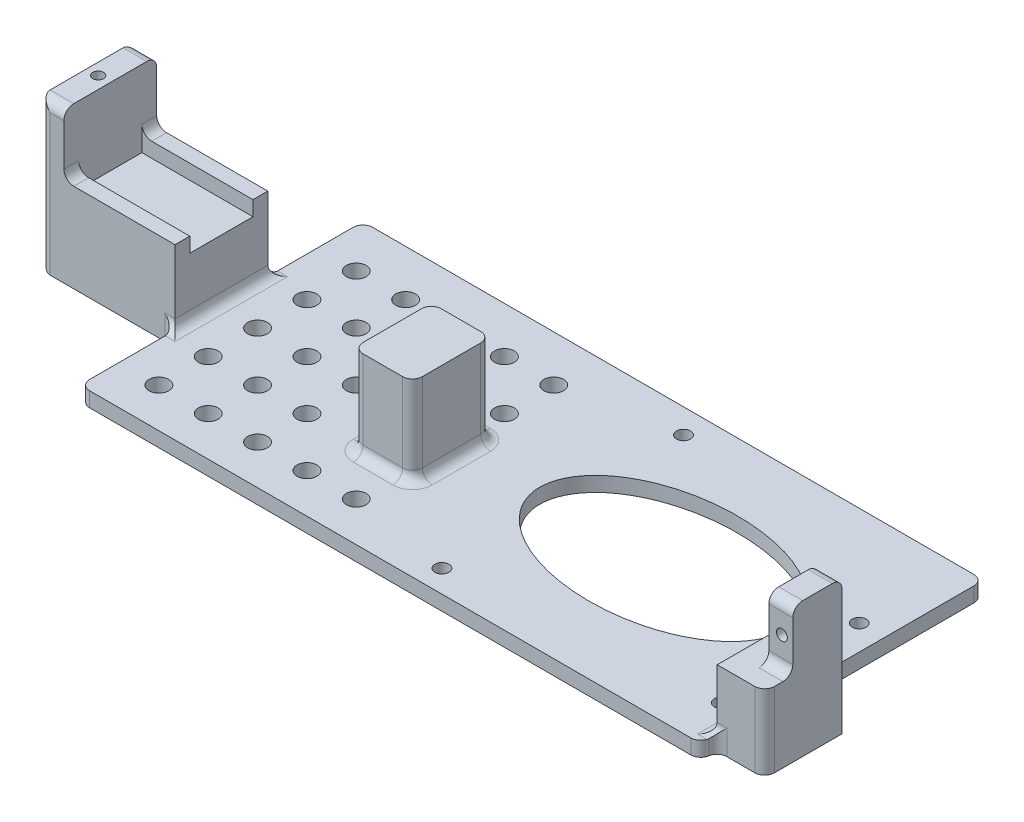
SolidWorks part; units mm, degrees
ref_plane "Front Plane" through (0, 0, 0) normal (0, 0, 1) x (1, 0, 0)
ref_plane "Top Plane" through (0, 0, 0) normal (0, 1, 0) x (1, 0, 0)
ref_plane "Right Plane" through (0, 0, 0) normal (1, 0, 0) x (0, 0, -1)
sketch "Arduino Base" plane through (0, 0, 0) normal (0, 1, 0) x (1, 0, 0)
  line L0 (-36.29, 28.67) -> (36.29, 28.67)
  line L1 (-34.29, -26.67) -> (34.29, -26.67) construction
  line L2 (-34.29, -26.67) -> (-34.29, 26.67) construction
  line L3 (-34.29, 26.67) -> (34.29, 26.67) construction
  line L4 (34.29, -26.67) -> (34.29, 26.67) construction
  line L5 (-34.29, -26.67) -> (34.29, 26.67) construction
  line L6 (-34.29, 26.67) -> (34.29, -26.67) construction
  line L7 (36.29, -28.67) -> (36.29, 28.67)
  line L8 (-36.29, -28.67) -> (36.29, -28.67)
  line L9 (-36.29, -28.67) -> (-36.29, 28.67)
  circle A0 centre (-19.59, 23.71) radius 1.4224
  circle A1 centre (31.21, 8.51) radius 1.4224
  circle A2 centre (31.21, -19.43) radius 1.4224
  circle A3 centre (-20.69, -24.13) radius 1.4224
  point P0 (0, 0)
  dimension "D3" = 2.8448
  dimension "D4" = 2.54
  dimension "D11" = 2
  dimension "D1" = 53.34
  dimension "D2" = 68.58
  dimension "D5" = 27.94
  dimension "D6" = 4.7
  dimension "D7" = 50.8
  dimension "D8" = 15.2
  dimension "D9" = 51.9
  dimension "D10" = 65.5
extrude "Arduino" add sketch "Arduino Base" along normal blind 3
sketch "Sketch5" plane through (0, 0, 0) normal (0, -1, 0) x (1, 0, 0)
  ellipse E0 centre (0, 0) end of major axis (-25, 0) minor radius 15
  dimension "D1" = 15
  dimension "D2" = 25
extrude "Cut-Extrude1" cut sketch "Sketch5" against normal up to surface (3 mm away) up to face at (0, 3, 0)
fillet "Fillet2" radius 2 2 edges at (36.29, 1.5, -28.67) (36.29, 1.5, 28.67)
sketch "Battery Base" plane through (-36.29, 0, 0) normal (-1, 0, 0) x (0, 0, 1)
  line L1 (-28.67, 3) -> (28.67, 3)
  line L2 (-28.67, 3) -> (-28.67, 0)
  line L3 (-28.67, 0) -> (28.67, 0)
  line L4 (28.67, 3) -> (28.67, 0)
extrude "Battery" add sketch "Battery Base" along normal blind 53.2
sketch "Sketch4" plane through (0, 3, 0) normal (0, 1, 0) x (1, 0, 0)
  line L0 (-89.49, -28.67) -> (34.29, -28.67) construction
  line L1 (-89.49, 28.67) -> (-36.29, 28.67) construction
  line L2 (-89.49, 28.67) -> (-89.49, -28.67) construction
  line L3 (-89.49, -28.67) -> (-36.29, -28.67) construction
  line L4 (-36.29, 28.67) -> (-36.29, -28.67) construction
  line L5 (-38.29, -12.49) -> (-50.29, -12.49)
  line L6 (-36.29, 5.33) -> (-52.29, 5.33) construction
  line L7 (-36.29, 5.33) -> (-36.29, -14.49) construction
  line L8 (-36.29, -14.49) -> (-52.29, -14.49) construction
  line L9 (-52.29, 5.33) -> (-52.29, -14.49) construction
  line L10 (-50.29, 3.33) -> (-50.29, -12.49)
  line L11 (-38.29, 3.33) -> (-50.29, 3.33)
  line L12 (-38.29, 3.33) -> (-38.29, -12.49)
  line L13 (-38.29, 28.67) -> (-38.29, -28.67) construction
  line L14 (-36.29, 3.33) -> (-50.29, 3.33) construction
  line L15 (-36.29, -12.49) -> (-50.29, -12.49) construction
  dimension "D1" = 53.2
  dimension "D2" = 14.18
  dimension "D3" = 34
  dimension "D4" = 16
  dimension "D5" = 2
extrude "Boss-Extrude3" add sketch "Sketch4" along normal blind 18
fillet "Fillet1" radius 2 8 edges at (-38.29, 12, -3.33) (-38.29, 12, 12.49) (-50.29, 12, 12.49) (-50.29, 12, -3.33) (-44.29, 3, 12.49) (-38.29, 3, 4.58) (-50.29, 3, 4.58) (-44.29, 3, -3.33)
sketch "Sketch6" plane through (0, 3, 0) normal (0, 1, 0) x (1, 0, 0)
  line L0 (-89.49, -28.67) -> (-89.49, 28.67) construction
  line L1 (-89.49, 6.4) -> (-111.99, 6.4)
  line L2 (-89.49, 6.4) -> (-89.49, -6.4)
  line L3 (-89.49, -6.4) -> (-111.99, -6.4)
  line L4 (-111.99, 6.4) -> (-111.99, -6.4)
  point P6 (-89.49, 0)
  point P7 (-89.49, 0)
  dimension "D1" = 22.5
  dimension "D2" = 12.8
extrude "Boss-Extrude4" add sketch "Sketch6" against normal up to surface (3 mm away) and the other way blind 12 up to face at (-25, 0, 0)
sketch "Sketch7" plane through (0, 0, 6.4) normal (0, 0, 1) x (1, 0, 0)
  line L0 (-111.99, 15) -> (-89.49, 15) construction
  line L1 (-89.49, 0) -> (-114.99, 0)
  line L2 (-89.49, 0) -> (-89.49, 18)
  line L3 (-89.49, 18) -> (-114.99, 18)
  line L4 (-114.99, 0) -> (-114.99, 18)
  line L5 (-111.99, 15) -> (-111.99, 0) construction
  dimension "D1" = 3
  dimension "D2" = 3
extrude "Boss-Extrude5" add sketch "Sketch7" along normal blind 3
mirror "Mirror1" about plane through (0, 0, 0) normal (0, 0, 1) of "Boss-Extrude5"
sketch "Sketch8" plane through (-111.99, 0, 0) normal (-1, 0, 0) x (0, 0, 1)
  line L1 (-6.4, 18) -> (6.4, 18)
  line L2 (-6.4, 18) -> (-6.4, 0)
  line L3 (-6.4, 0) -> (6.4, 0)
  line L4 (6.4, 18) -> (6.4, 0)
extrude "Boss-Extrude6" add sketch "Sketch8" along normal up to surface (3 mm away) up to face at (-114.99, 9, -7.9)
sketch "Sketch10" plane through (-114.99, 0, 0) normal (-1, 0, 0) x (0, 0, 1)
  line L0 (9.4, 18) -> (9.4, 0) construction
  line L1 (-9.4, 0) -> (9.4, 0)
  line L2 (-9.4, 0) -> (-9.4, 30.5)
  line L3 (-9.4, 30.5) -> (9.4, 30.5)
  line L4 (9.4, 0) -> (9.4, 30.5)
  dimension "D1" = 30.5
extrude "Boss-Extrude7" add sketch "Sketch10" along normal blind 1.8 and the other way up to surface (3 mm away) other way up to face at (-111.99, 16.5, 0)
fillet "Fillet4" radius 2 2 edges at (-111.99, 18, 7.9) (-111.99, 18, -7.9)
sketch "Sketch11" plane through (0, 30.5, 0) normal (0, 1, 0) x (1, 0, 0)
  line L0 (-111.99, 9.4) -> (-116.79, 9.4) construction
  line L1 (-111.99, 9.4) -> (-111.99, -9.4) construction
  circle A0 centre (-114.45, 0) radius 1.1
  dimension "D1" = 2.2
  dimension "D2" = 9.4
  dimension "D3" = 2.46
extrude "Cut-Extrude2" cut sketch "Sketch11" against normal up to surface (15.5 mm away) up to face at (-100.74, 15, 0)
fillet "Fillet5" radius 2 2 edges at (-89.49, 1.5, -9.4) (-89.49, 1.5, 9.4)
fillet "Fillet6" radius 2 1 edges at (-89.49, 3, 0)
fillet "Fillet7" radius 2 5 edges at (-116.79, 0, 0) (-116.79, 15.25, -9.4) (-116.79, 15.25, 9.4) (-114.39, 30.5, -9.4) (-114.39, 30.5, 9.4)
sketch "Sketch12" plane through (0, 0, 0) normal (0, -1, 0) x (1, 0, 0)
  line L0 (36.29, 25.33) -> (56.29, 25.33) construction
  line L1 (36.29, 26.67) -> (36.29, -26.67) construction
  line L2 (-89.49, 28.67) -> (34.29, 28.67) construction
  line L4 (36.29, 25.33) -> (45.89, 25.33)
  line L5 (36.29, 25.33) -> (36.29, 9.63)
  line L6 (36.29, 9.63) -> (45.89, 9.63)
  line L7 (45.89, 25.33) -> (45.89, 9.63)
  dimension "D1" = 3.34
  dimension "D2" = 20
  dimension "D3" = 15.7
  dimension "D4" = 9.6
extrude "Boss-Extrude8" add sketch "Sketch12" against normal blind 15.16
fillet "Fillet8" radius 2 1 edges at (36.29, 3, 17.48)
sketch "Sketch13" plane through (0, 15.16, 0) normal (0, 1, 0) x (1, 0, 0)
  line L1 (45.89, -9.63) -> (41.04, -9.63)
  line L2 (45.89, -9.63) -> (45.89, -19.63)
  line L3 (45.89, -19.63) -> (41.04, -19.63)
  line L4 (41.04, -9.63) -> (41.04, -19.63)
  dimension "D1" = 10
  dimension "D2" = 4.85
extrude "Boss-Extrude9" add sketch "Sketch13" along normal blind 12.2
fillet "Fillet9" radius 2 2 edges at (36.29, 1.5, 9.63) (36.29, 1.5, 25.33)
sketch "Sketch14" plane through (0, 0, 9.63) normal (0, 0, -1) x (-1, 0, 0)
  line L0 (-45.89, 27.36) -> (-41.04, 27.36) construction
  line L1 (-45.89, 27.36) -> (-45.89, 0) construction
  circle A0 centre (-43.69, 21.26) radius 1.1
  dimension "D1" = 2.2
  dimension "D2" = 6.1
  dimension "D3" = 2.2
extrude "Cut-Extrude3" cut sketch "Sketch14" against normal up to surface (10 mm away) up to face at (43.465, 21.26, 19.63)
fillet "Fillet10" radius 2 2 edges at (-89.49, 1.5, 28.67) (-89.49, 1.5, -28.67)
sketch "Sketch15" plane through (0, 0, 0) normal (0, -1, 0) x (1, 0, 0)
  line L0 (-89.49, 11.4) -> (-89.49, 26.67) construction
  line L1 (-87.49, 28.67) -> (34.29, 28.67) construction
  circle A0 centre (-81.49, 20.67) radius 2
  circle A1 centre (-71.49, 20.67) radius 2
  circle A2 centre (-61.49, 20.67) radius 2
  circle A3 centre (-51.49, 20.67) radius 2
  circle A4 centre (-41.49, 20.67) radius 2
  circle A5 centre (-71.49, 10.67) radius 2
  circle A6 centre (-61.49, 10.67) radius 2
  circle A9 centre (-71.49, 0.67) radius 2
  circle A10 centre (-61.49, 0.67) radius 2
  circle A13 centre (-71.49, -9.33) radius 2
  circle A14 centre (-61.49, -9.33) radius 2
  circle A15 centre (-51.49, -9.33) radius 2
  circle A16 centre (-41.49, -9.33) radius 2
  circle A17 centre (-71.49, -19.33) radius 2
  circle A18 centre (-61.49, -19.33) radius 2
  circle A19 centre (-51.49, -19.33) radius 2
  circle A20 centre (-41.49, -19.33) radius 2
  circle A21 centre (-81.49, 10.67) radius 2
  circle A22 centre (-81.49, 0.67) radius 2
  circle A23 centre (-81.49, -9.33) radius 2
  circle A24 centre (-81.49, -19.33) radius 2
  circle A25 centre (-51.49, 0.67) radius 2 [skipped]
  circle A26 centre (-41.49, 0.67) radius 2 [skipped]
  circle A27 centre (-51.49, 10.67) radius 2 [skipped]
  circle A28 centre (-41.49, 10.67) radius 2 [skipped]
  dimension "D1" = 4
  dimension "D2" = 8
  dimension "D3" = 8
  dimension "D4" = 5
  dimension "D5" = 5
extrude "Cut-Extrude4" cut sketch "Sketch15" against normal up to surface (3 mm away) up to face at (-25, 3, 0)
fillet "Fillet11" radius 2 4 edges at (43.465, 27.36, 9.63) (43.465, 27.36, 19.63) (43.465, 15.16, 19.63) (45.89, 7.58, 25.33)
fillet "Fillet12" radius 2 1 edges at (-89.49, 3, 9.4)
fillet "Fillet13" radius 2 1 edges at (-89.49, 3, -9.4)
fillet "Fillet14" radius 2 2 edges at (36.29, 3, 9.63) (36.2626, 3, 25.33)
